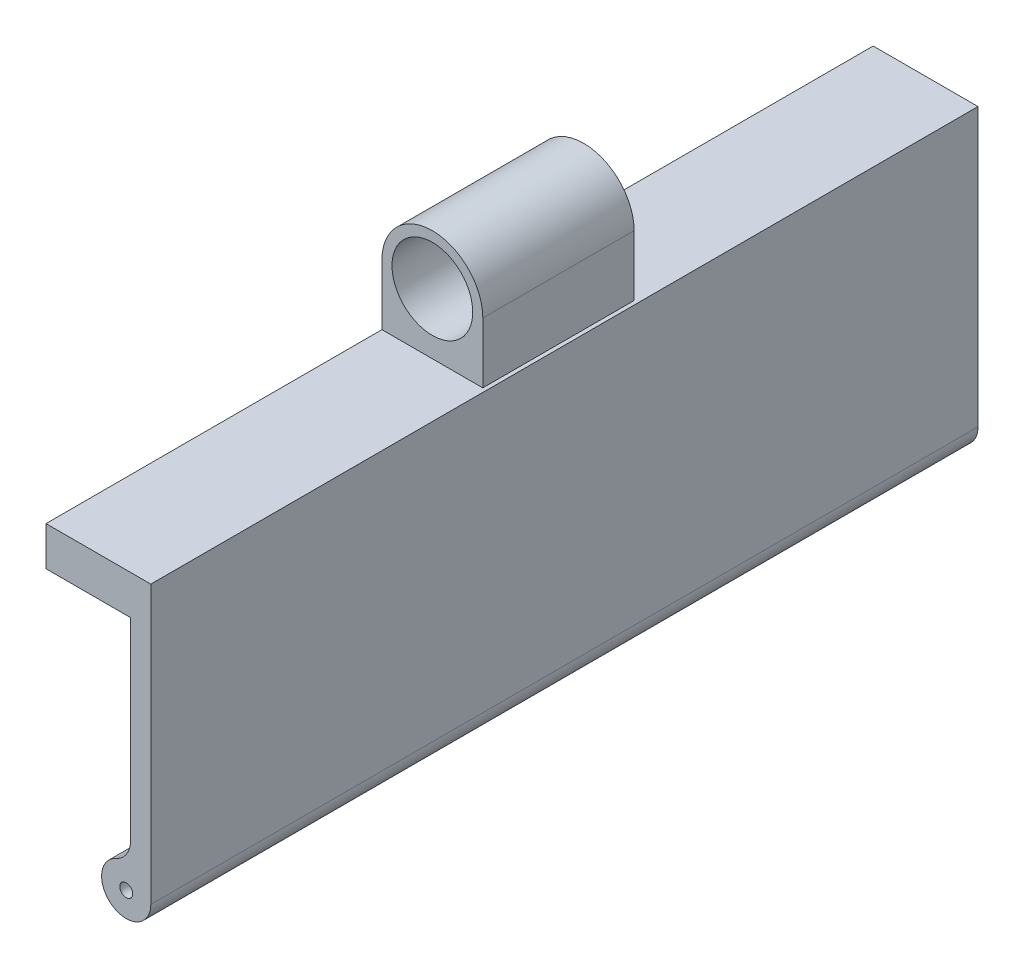
SolidWorks part; units mm, degrees
ref_plane "Front Plane" through (0, 0, 0) normal (0, 0, 1) x (1, 0, 0)
ref_plane "Top Plane" through (0, 0, 0) normal (0, 1, 0) x (1, 0, 0)
ref_plane "Right Plane" through (0, 0, 0) normal (1, 0, 0) x (0, 0, -1)
sketch "Sketch1" plane through (0, 0, 0) normal (0, 0, 1) x (1, 0, 0)
  line L0 (0, 0) -> (3.1723, 0) construction
  line L1 (2.44, 0) -> (2.44, 25)
  line L2 (0.44, 4.49) -> (0.44, 25)
  line L3 (0.44, 25) -> (2.44, 25)
  circle A0 centre (0, 0) radius 0.64
  arc A1 (-1.0175, 2.2177) -> (2.44, 0) centre (0, 0) ccw
  arc A2 (0.44, 4.49) -> (-1.0175, 2.2177) centre (-2.06, 4.49) cw
  dimension "D1" = 1.28
  dimension "D2" = 4.88
  dimension "D5" = 2.5
  dimension "D3" = 25
  dimension "D4" = 2
extrude "Boss-Extrude1" add sketch "Sketch1" along normal blind 82
sketch "Sketch3" plane through (0, 25, 0) normal (0, 1, 0) x (1, 0, 0)
  line L1 (0.44, -82) -> (2.44, -82)
  line L2 (0.44, -82) -> (0.44, 0)
  line L3 (0.44, 0) -> (2.44, 0)
  line L4 (2.44, -82) -> (2.44, 0)
extrude "Boss-Extrude4" add sketch "Sketch3" along normal blind 2.5
sketch "Sketch6" plane through (0.44, 0, 0) normal (-1, 0, 0) x (0, 0, 1)
  line L1 (82, 27.5) -> (0, 27.5)
  line L2 (82, 27.5) -> (82, 23.6193)
  line L3 (82, 23.6193) -> (0, 23.6193)
  line L4 (0, 27.5) -> (0, 23.6193)
  dimension "D1" = 23.01
extrude "Boss-Extrude5" add sketch "Sketch6" along normal blind 8.39
ref_plane "Plane2" through (-7.95, 23.6193, 0) normal (0, 0, 1) x (1, 0, 0)
ref_plane "Plane3" through (-7.95, 23.6193, 82) normal (0, 0, 1) x (1, 0, 0)
ref_plane "Plane4" through (0.44, 23.6193, 82) normal (0, 0, 1) x (1, 0, 0)
sketch "Sketch8" plane through (0, 0, 0) normal (0, 0, -1) x (-1, 0, 0)
  line L0 (7.95, 27.5) -> (7.95, 33.5)
  line L1 (-2.05, 33.5) -> (-2.05, 27.5)
  line L2 (-2.44, 27.5) -> (7.95, 27.5) construction
  line L3 (7.95, 27.5) -> (-2.05, 27.5)
  circle A0 centre (2.95, 33.5) radius 4
  arc A1 (7.95, 33.5) -> (-2.05, 33.5) centre (2.95, 33.5) ccw
extrude "Boss-Extrude6" add sketch "Sketch8" against normal blind 15 from offset 33.7 offset against normal yes
